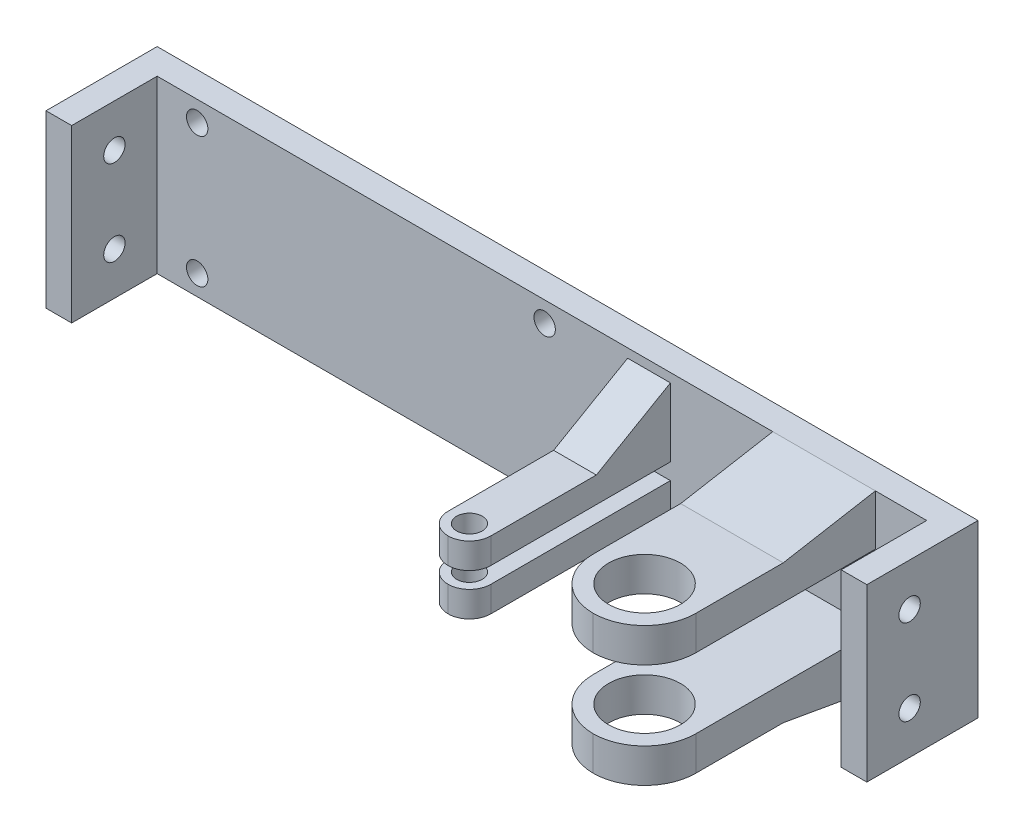
SolidWorks part; units mm, degrees
ref_plane "Piano frontale" through (0, 0, 0) normal (0, 0, 1) x (1, 0, 0)
ref_plane "Piano superiore" through (0, 0, 0) normal (0, 1, 0) x (1, 0, 0)
ref_plane "Piano destro" through (0, 0, 0) normal (1, 0, 0) x (0, 0, -1)
sketch "Schizzo1" plane through (0, 0, 0) normal (0, 0, 1) x (1, 0, 0)
  line L0 (-45, 0) -> (5, 0) construction
  line L1 (48, -10) -> (-48, -10)
  line L2 (48, -10) -> (48, 10)
  line L3 (48, 10) -> (-48, 10)
  line L4 (-48, -10) -> (-48, 10)
  line L5 (48, -10) -> (-48, 10) construction
  line L6 (48, 10) -> (-48, -10) construction
  line L7 (5, 0) -> (21, 0) construction
  line L8 (21, 0) -> (45, 0) construction
  line L9 (-45, 0) -> (-48, 0) construction
  line L10 (0.32, -7.62) -> (-40.32, -7.62) construction
  line L11 (0.32, -7.62) -> (0.32, 7.62) construction
  line L12 (0.32, 7.62) -> (-40.32, 7.62) construction
  line L13 (-40.32, -7.62) -> (-40.32, 7.62) construction
  line L14 (0.32, -7.62) -> (-40.32, 7.62) construction
  line L15 (0.32, 7.62) -> (-40.32, -7.62) construction
  line L16 (45, 0) -> (48, 0) construction
  circle A0 centre (20.125, 0) radius 0.875 construction
  circle A1 centre (20.125, 0) radius 1
  circle A2 centre (-40.32, 7.62) radius 1.25
  circle A3 centre (0.32, 7.62) radius 1.25
  circle A4 centre (0.32, -7.62) radius 1.25
  circle A5 centre (-40.32, -7.62) radius 1.25
  point P0 (0, 0)
  point P10 (-20, 0)
  dimension "D3" = 1.75
  dimension "D6" = 2
  dimension "D9" = 2.5
  dimension "D1" = 96
  dimension "D2" = 20
  dimension "D4" = 50
  dimension "D5" = 24
  dimension "D7" = 40.64
  dimension "D8" = 15.24
  dimension "D10" = 3
extrude "Estrusione-Estrusione1" add sketch "Schizzo1" along normal blind 3
sketch "Schizzo2" plane through (0, 0, 3) normal (0, 0, 1) x (1, 0, 0)
  line L0 (48, 10) -> (-48, 10) construction
  line L1 (45, -10) -> (-45, -10)
  line L2 (45, -10) -> (45, 10)
  line L3 (45, 10) -> (-45, 10)
  line L4 (-45, -10) -> (-45, 10)
  line L5 (45, -10) -> (-45, 10) construction
  line L6 (45, 10) -> (-45, -10) construction
  line L7 (-48, 10) -> (-48, -10) construction
  line L12 (-48, 10) -> (-48, -10)
  line L13 (-48, -10) -> (48, -10)
  line L14 (48, -10) -> (48, 10)
  line L15 (48, 10) -> (-48, 10)
  line L16 (-48, 10) -> (-48, -10)
  line L17 (-48, -10) -> (48, -10)
  line L18 (48, -10) -> (48, 10)
  line L19 (48, 10) -> (-48, 10)
  point P0 (0, 0)
  line M8 (-48, 10) -> (-48, -10)
  line M9 (-48, -10) -> (48, -10)
  line M10 (48, -10) -> (48, 10)
  line M11 (48, 10) -> (-48, 10)
  dimension "D1" = 3
  dimension "D2" = 0
extrude "Estrusione-Estrusione2" add sketch "Schizzo2" along normal blind 10 contours L4 M9 M11 M8 | L2 M9 M10 M11 region at (46.5, 0, 3) region at (-46.5, 0, 3)
sketch "Schizzo3" plane through (-48, 0, 0) normal (-1, 0, 0) x (0, 0, 1)
  line L0 (13, 10) -> (0, 10) construction
  line L1 (13, -10) -> (3, -10)
  line L2 (13, -10) -> (13, 10)
  line L3 (13, 10) -> (3, 10)
  line L4 (3, -10) -> (3, 10)
  line L5 (0, 10) -> (0, -10) construction
  line L6 (8, -10) -> (8, 10) construction
  line L7 (8, -10) -> (8, 0)
  line L8 (8, 0) -> (8, 10)
  circle A0 centre (8, -5) radius 1.25
  circle A1 centre (8, 5) radius 1.25
  dimension "D2" = 2.5
  dimension "D1" = 3
extrude "Taglio-Estrusione1" cut sketch "Schizzo3" against normal through all contours A0 | A1
sketch "Schizzo4" plane through (0, 0, 3) normal (0, 0, 1) x (1, 0, 0)
  line L0 (45, 0) -> (21, 0) construction
  line L1 (39, -8.1) -> (27, -8.1)
  line L2 (39, -8.1) -> (39, -4.1)
  line L3 (39, -4.1) -> (27, -4.1)
  line L4 (27, -8.1) -> (27, -4.1)
  line L5 (39, 4.1) -> (27, 4.1)
  line L6 (39, 4.1) -> (39, 8.1)
  line L7 (39, 8.1) -> (27, 8.1)
  line L8 (27, 4.1) -> (27, 8.1)
  line L9 (45, -10) -> (45, 10) construction
  line L10 (33, -4.1) -> (33, 4.1) construction
  point P16 (33, 0)
  dimension "D1" = 24
  dimension "D2" = 8.2
  dimension "D3" = 12
  dimension "D4" = 4
extrude "Estrusione-Estrusione3" add sketch "Schizzo4" along normal blind 27
fillet "Raccordo1" radius 6 4 edges at (27, 6.1, 30) (39, 6.1, 30) (39, -6.1, 30) (27, -6.1, 30)
sketch "Schizzo5" plane through (0, 8.1, 0) normal (0, 1, 0) x (1, 0, 0)
  circle A0 centre (33, -24) radius 4.2
  dimension "D1" = 8.4
extrude "Taglio-Estrusione2" cut sketch "Schizzo5" against normal through all
chamfer "Smusso1" distance 1.9 angle 80 2 edges at (33, 8.1, 3) (33, -8.1, 3) first distance on face at (0, 0, 3)
sketch "Schizzo6" plane through (0, 0, 3) normal (0, 0, 1) x (1, 0, 0)
  line L0 (20.125, 0) -> (12.525, 0) construction
  line L1 (12.525, 0.95) -> (12.525, -0.95) construction
  line L3 (15.025, 3.95) -> (10.025, 3.95)
  line L4 (15.025, 3.95) -> (15.025, 0.95)
  line L5 (15.025, 0.95) -> (10.025, 0.95)
  line L6 (10.025, 3.95) -> (10.025, 0.95)
  line L7 (15.025, -0.95) -> (10.025, -0.95)
  line L8 (15.025, -0.95) -> (15.025, -3.95)
  line L9 (15.025, -3.95) -> (10.025, -3.95)
  line L10 (10.025, -0.95) -> (10.025, -3.95)
  dimension "D1" = 7.6
  dimension "D2" = 1.9
  dimension "D3" = 5
  dimension "D4" = 3
extrude "Estrusione-Estrusione4" add sketch "Schizzo6" along normal blind 23.5
fillet "Raccordo2" radius 2.5 4 edges at (15.025, -2.45, 26.5) (10.025, -2.45, 26.5) (15.025, 2.45, 26.5) (10.025, 2.45, 26.5)
sketch "Schizzo7" plane through (0, 3.95, 0) normal (0, 1, 0) x (1, 0, 0)
  circle A0 centre (12.525, -24) radius 1.5
  dimension "D1" = 3
extrude "Taglio-Estrusione3" cut sketch "Schizzo7" against normal through all
chamfer "Smusso2" distance 5 angle 60 2 edges at (12.525, -3.95, 3) (12.525, 3.95, 3) first distance on face at (22, 0, 3)
